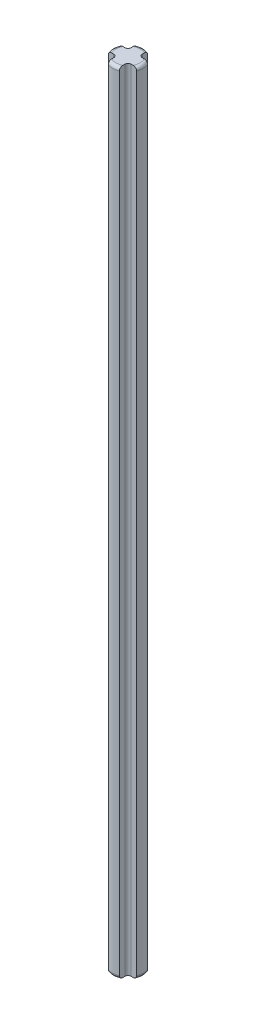
SolidWorks part; units mm, degrees
material "ABS"
ref_plane "Front Plane" through (0, 0, 0) normal (0, 0, 1) x (1, 0, 0)
ref_plane "Top Plane" through (0, 0, 0) normal (0, 1, 0) x (1, 0, 0)
ref_plane "Right Plane" through (0, 0, 0) normal (1, 0, 0) x (0, 0, -1)
ref_plane "Plane1" through (0, 0, 0) normal (0, 0, -1) x (-1, 0, 0)
sketch "Sketch1" plane through (0, 0, 0) normal (0, 0, -1) x (-1, 0, 0)
  line L0 (-2.39, 0) -> (0, 0)
  line L1 (0, 0) -> (0, 124)
  line L2 (0, 124) -> (-2.39, 124)
  line L3 (-2.39, 124) -> (-2.39, 0)
  line L4 (0, 0) -> (0, 124) construction
  dimension "D1" = 2.39
  dimension "D2" = 124
revolve "Revolve1" add sketch "Sketch1" angle 360 about L4 reverse direction yes
sketch "Sketch2" plane through (0, 0, 0) normal (0, -1, 0) x (1, 0, 0)
  line L0 (0.875, 2.2241) -> (0.875, 0.875)
  line L1 (0.875, 0.875) -> (2.2241, 0.875)
  line L2 (2.629, 0) -> (-2.629, 0) construction
  line L3 (0, -2.629) -> (0, 2.629) construction
  line L4 (-2.39, 0) -> (2.39, 0) construction
  line L5 (0, 2.39) -> (0, -2.39) construction
  line L6 (0.875, -0.875) -> (2.2241, -0.875)
  line L7 (0.875, -2.2241) -> (0.875, -0.875)
  line L8 (-0.875, -2.2241) -> (-0.875, -0.875)
  line L9 (-0.875, -0.875) -> (-2.2241, -0.875)
  line L10 (-0.875, 0.875) -> (-2.2241, 0.875)
  line L11 (-0.875, 2.2241) -> (-0.875, 0.875)
  arc A0 (2.2241, 0.875) -> (0.875, 2.2241) centre (0, 0) ccw
  circle A1 centre (0, 0) radius 1.2374 construction
  circle A3 centre (0, 0) radius 2.39 construction
  arc A4 (2.2241, -0.875) -> (0.875, -2.2241) centre (0, 0) cw
  arc A5 (-2.2241, -0.875) -> (-0.875, -2.2241) centre (0, 0) ccw
  arc A6 (-2.2241, 0.875) -> (-0.875, 2.2241) centre (0, 0) cw
  dimension "D2" = 2.39
  dimension "D1" = 2.4749
  dimension "D3" = 1.3491
extrude "Cut-Extrude1" cut sketch "Sketch2" against normal through all
fillet "Fillet1" radius 0.5 12 edges at (2.39, 0, 0) (0, 0, 2.39) (0, 124, 2.39) (0.875, 62, 0.875) (2.39, 124, 0) (-2.39, 124, 0) (0, 124, -2.39) (0.875, 62, -0.875) (-0.875, 62, -0.875) (0, 0, -2.39) (-2.39, 0, 0) (-0.875, 62, 0.875) tangent propagation no
sketch "Sketch6" [suppressed] plane through (0, 124, 0) normal (0, 1, 0) x (1, 0, 0)
  circle A0 centre (0, 0) radius 2.5795
extrude "Cut-Extrude5" [suppressed] cut sketch "Sketch6" against normal blind 91.74
fillet "Fillet2" [suppressed] radius 0.5
